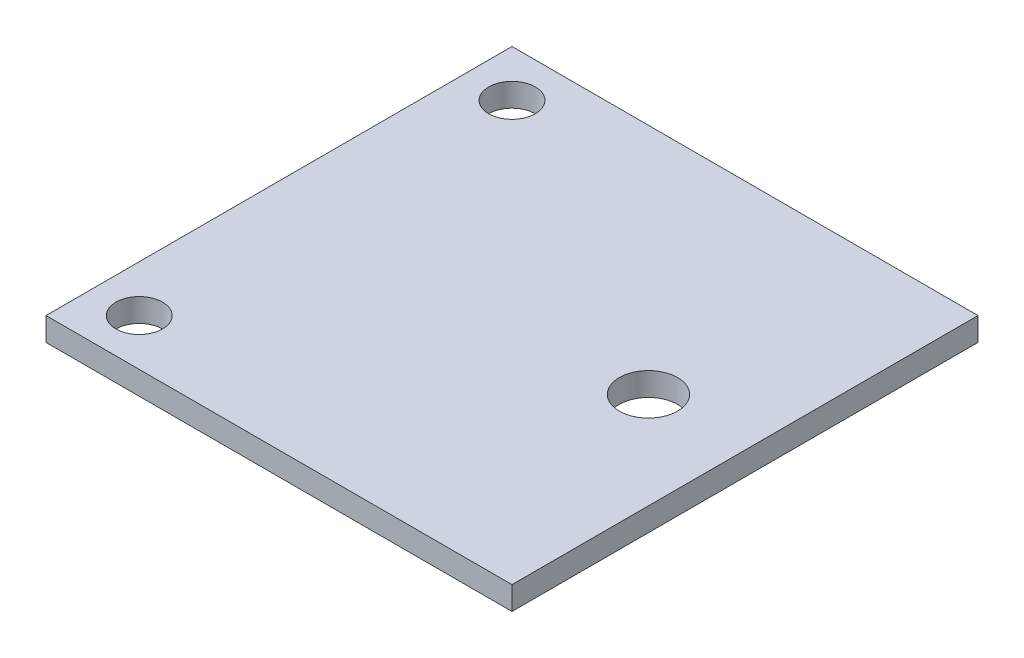
SolidWorks part; units mm, degrees
material "Cast Alloy Steel"
ref_plane "Front Plane" through (0, 0, 0) normal (0, 0, 1) x (1, 0, 0)
ref_plane "Top Plane" through (0, 0, 0) normal (0, 1, 0) x (1, 0, 0)
ref_plane "Right Plane" through (0, 0, 0) normal (1, 0, 0) x (0, 0, -1)
sketch "Sketch1" plane through (0, 0, 0) normal (0, 1, 0) x (1, 0, 0)
  line L0 (12.7, 50.8) -> (12.7, -50.8) construction
  line L1 (0, -63.5) -> (127, -63.5)
  line L2 (0, -63.5) -> (0, 63.5)
  line L3 (0, 63.5) -> (127, 63.5)
  line L4 (127, -63.5) -> (127, 63.5)
  line L5 (0, 63.5) -> (12.7, 50.8) construction
  line L6 (0, -63.5) -> (12.7, -50.8) construction
  line L7 (12.7, -50.8) -> (100.6882, 0) construction
  line L8 (100.6882, 0) -> (12.7, 50.8) construction
  circle A0 centre (12.7, 50.8) radius 6.35
  circle A1 centre (12.7, -50.8) radius 6.35
  circle A2 centre (100.6882, 0) radius 7.9375
  point P0 (0, 0)
  point P13 (0, 0)
  dimension "D2" = 12.7
  dimension "D3" = 12.7
  dimension "D4" = 101.6
  dimension "D1" = 15.875
  dimension "D6" = 45
  dimension "D7" = 45
  dimension "D5" = 127
extrude "Boss-Extrude1" add sketch "Sketch1" along normal blind 6.35
